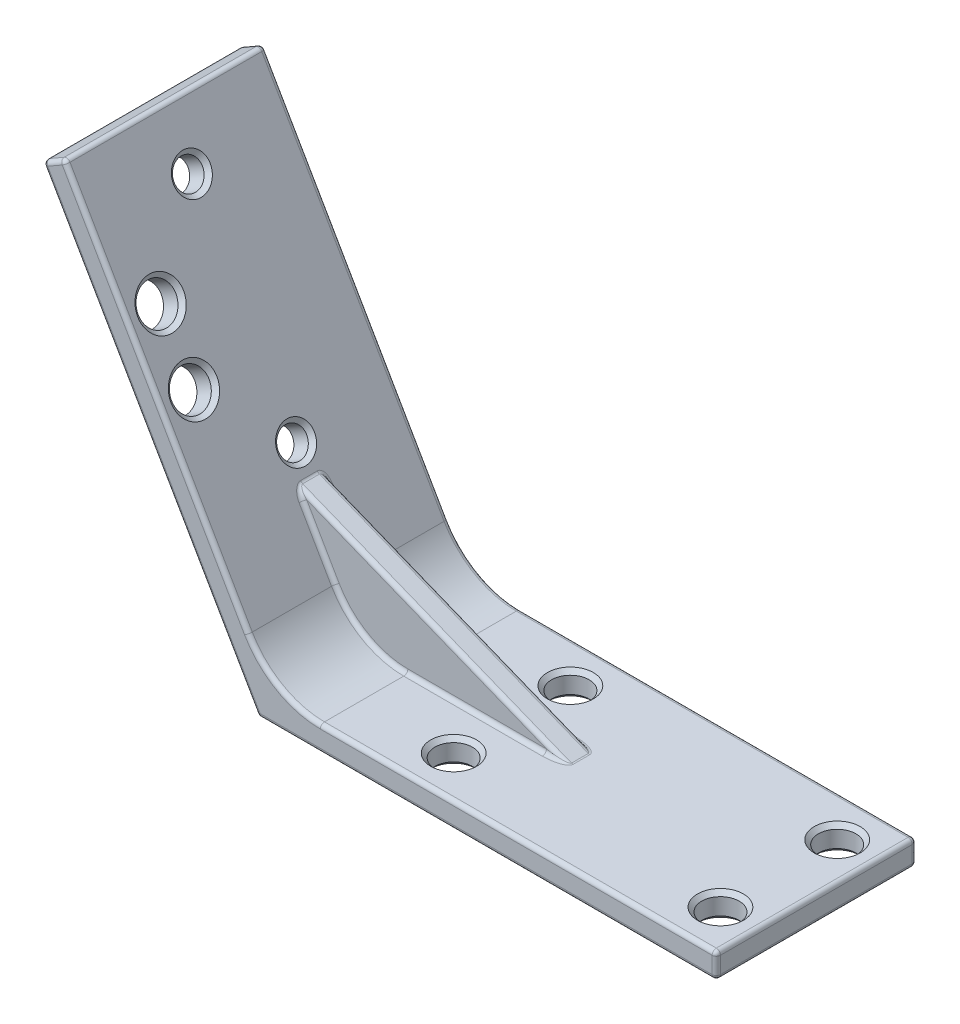
SolidWorks part; units mm, degrees
ref_plane "前视基准面" through (0, 0, 0) normal (0, 0, 1) x (1, 0, 0)
ref_plane "上视基准面" through (0, 0, 0) normal (0, 1, 0) x (1, 0, 0)
ref_plane "右视基准面" through (0, 0, 0) normal (1, 0, 0) x (0, 0, -1)
other "Configuration Table"
sketch "草图1" plane through (0, 0, 0) normal (0, 0, 1) x (1, 0, 0)
  line L0 (-27.5, -1.5) -> (-53.366, 43.3013)
  line L1 (-27.5, -1.5) -> (27.5, -1.5)
  line L2 (-27.5, -1.5) -> (-27.5, 1.5)
  line L3 (-27.5, 1.5) -> (27.5, 1.5)
  line L4 (27.5, -1.5) -> (27.5, 1.5)
  line L5 (-27.5, -1.5) -> (27.5, 1.5) construction
  line L6 (-27.5, 1.5) -> (27.5, -1.5) construction
  line L7 (-53.366, 43.3013) -> (-50.7679, 44.8013)
  line L8 (-50.7679, 44.8013) -> (-25.7679, 1.5)
  point P0 (0, 0)
  dimension "D1" = 55
  dimension "D2" = 3
  dimension "D3" = 3
  dimension "D4" = 50
  dimension "D5" = 120
extrude "凸台-拉伸1" add sketch "草图1" along normal mid plane 24 contours L8 L7 L0 L2 L3 | L2 L1 L4 L3 region at (-39.572, 22.392, 0)
sketch "草图2" plane through (0, 1.5, 0) normal (0, 1, 0) x (1, 0, 0)
  line L0 (27.5, -12) -> (27.5, 12) construction
  line L1 (-9, -7) -> (23, -7) construction
  line L2 (-9, -7) -> (-9, 7) construction
  line L3 (-9, 7) -> (23, 7) construction
  line L4 (23, -7) -> (23, 7) construction
  line L5 (-9, -7) -> (23, 7) construction
  line L6 (-9, 7) -> (23, -7) construction
  circle A0 centre (-9, 7) radius 2.25
  circle A1 centre (-9, -7) radius 2.25
  circle A2 centre (23, -7) radius 2.25
  circle A3 centre (23, 7) radius 2.25
  point P0 (7, 0)
  point P10 (4.2761, -0.2185)
  dimension "D3" = 4.5
  dimension "D1" = 32
  dimension "D2" = 14
  dimension "D4" = 4.5
extrude "切除-拉伸1" cut sketch "草图2" against normal blind 20
sketch "草图3" plane through (0, 0, 0) normal (0, 0, 1) x (1, 0, 0)
  line L0 (-33.2679, 14.4904) -> (-25.7679, 1.5)
  line L1 (-50.7679, 44.8013) -> (-25.7679, 1.5) construction
  line L2 (-25.7679, 1.5) -> (-0.7679, 1.5)
  line L3 (-25.7679, 1.5) -> (27.5, 1.5) construction
  line L4 (-0.7679, 1.5) -> (-33.2679, 14.4904)
  dimension "D1" = 25
  dimension "D2" = 15
extrude "凸台-拉伸2" add sketch "草图3" along normal mid plane 3
sketch "草图4" plane through (-21.2745, -12.2828, 0) normal (-0.866, -0.5, 0) x (0, 0, 1)
  line L0 (0, 32.451) -> (0, 57.451) construction
  line L3 (12, 12.451) -> (-12, 12.451) construction
  line L5 (8, 40.951) -> (8, 48.951) construction
  line L6 (12, 12.451) -> (12, 64.183) construction
  line L7 (8, 44.951) -> (0, 44.951) construction
  circle A0 centre (0, 57.451) radius 1.7
  circle A1 centre (0, 32.451) radius 1.7
  circle A2 centre (8, 48.951) radius 2.25
  circle A3 centre (8, 40.951) radius 2.25
  dimension "D2" = 3.4
  dimension "D3" = 20
  dimension "D5" = 4.5
  dimension "D1" = 25
  dimension "D4" = 8
  dimension "D6" = 4
extrude "切除-拉伸2" cut sketch "草图4" against normal blind 3
fillet "圆角1" radius 10 2 edges at (-25.7679, 1.5, -6.75) (-25.7679, 1.5, 6.75)
fillet "圆角2" radius 0.5 29 edges at (27.5, -1.5, 0) (27.5, 1.5, 0) (-50.7679, 44.8013, 0) (-53.366, 43.3013, 0) (27.5, 0, -12) (3.7528, 1.5, -12) (-39.7113, 25.6506, -12) (-52.067, 44.0513, -12) (-40.433, 20.9006, -12) (0, -1.5, -12) (-52.067, 44.0513, 12) (-39.7113, 25.6506, 12) (-24.9944, 2.8397, 12) (3.7528, 1.5, 12) (27.5, 0, 12) (0, -1.5, 12) (-40.433, 20.9006, 12) (-27.5, -1.5, 0) (-0.7679, 1.5, 0) (-33.2679, 14.4904, 0) (-30.9613, 10.4952, -1.5) (-10.3812, 1.5, -1.5) (-17.0179, 7.9952, -1.5) (-17.0179, 7.9952, 1.5) (-10.3812, 1.5, 1.5) (-24.9944, 2.8397, 1.5) (-30.9613, 10.4952, 1.5) (-24.9944, 2.8397, -1.5) (-24.9944, 2.8397, -12)
chamfer "倒角1" distance 0.5 angle 45 16 edges at (23, -1.5, 9.25) (23, 1.5, 9.25) (23, -1.5, -4.75) (23, 1.5, -4.75) (-9, -1.5, 9.25) (-9, 1.5, 9.25) (-9, -1.5, -4.75) (-9, 1.5, -4.75) (-49.15, 35.9989, 0) (-46.5519, 37.4989, 0) (-44.625, 28.1614, 8) (-42.0269, 29.6614, 8) (-40.625, 21.2332, 8) (-38.0269, 22.7332, 8) (-36.65, 14.3483, 0) (-34.0519, 15.8483, 0)
